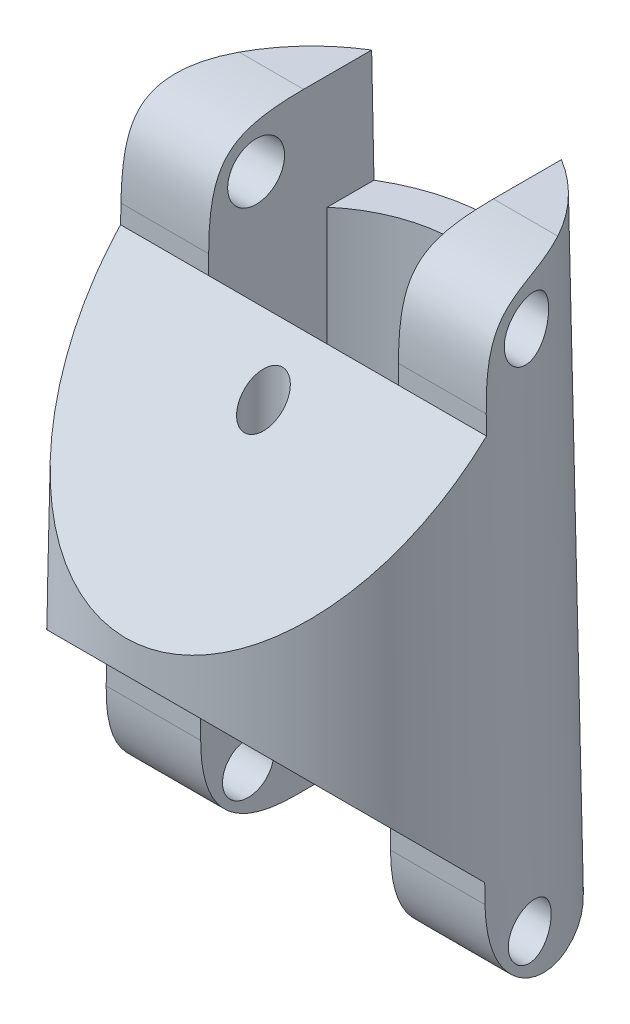
SolidWorks part; units mm, degrees
material "ABS"
ref_plane "Front Plane" through (0, 0, 0) normal (0, 0, 1) x (1, 0, 0)
ref_plane "Top Plane" through (0, 0, 0) normal (0, 1, 0) x (1, 0, 0)
ref_plane "Right Plane" through (0, 0, 0) normal (1, 0, 0) x (0, 0, -1)
sketch "Sketch1" plane through (0, 0, 0) normal (0, 1, 0) x (1, 0, 0)
  circle A0 centre (0, 0) radius 10
  dimension "D1" = 20
extrude "Boss-Extrude1" add sketch "Sketch1" along normal blind 26 draft 1 and the other way blind 6 draft 1
sketch "Sketch2" plane through (0, 0, 0) normal (1, 0, 0) x (0, 0, -1)
  line L0 (-0.4538, 26) -> (-0.4538, 20)
  line L2 (9.5462, 26) -> (-9.5462, 26) construction
  line L3 (-0.4538, 20) -> (-13.1885, 7.2653)
  line L5 (-13.1885, 7.2653) -> (-13.1885, 26)
  line L6 (-13.1885, 26) -> (-0.4538, 26)
  dimension "D1" = 10
  dimension "D2" = 6
  dimension "D3" = 135
extrude "Cut-Extrude1" cut sketch "Sketch2" against normal through all both and the other way through all
sketch "Sketch3" plane through (0, 0, 0.4538) normal (0, 0, 1) x (1, 0, 0)
  line L0 (-9.6402, 20) -> (9.6402, 20) construction
  line L1 (5, 26) -> (-5, 26)
  line L2 (5, 26) -> (5, 20)
  line L3 (5, 20) -> (-5, 20)
  line L4 (-5, 26) -> (-5, 20)
  line L5 (5, 26) -> (-5, 20) construction
  line L6 (5, 20) -> (-5, 26) construction
  point P0 (0, 23)
  dimension "D1" = 10
  dimension "D2" = 6
extrude "Cut-Extrude2" cut sketch "Sketch3" against normal blind 25
sketch "Sketch4" plane through (-5, 0, 0) normal (1, 0, 0) x (0, 0, -1)
  circle A0 centre (2.0462, 23.5) radius 1.5
  dimension "D3" = 3
  dimension "D1" = 2.5
  dimension "D2" = 2.5
extrude "Cut-Extrude3" cut sketch "Sketch4" against normal through all both and the other way through all
fillet "Fillet2" radius 5 2 edges at (7.2677, 26, 0.4538) (-7.2677, 26, 0.4538)
sketch "Sketch7" plane through (0, 0, 0) normal (1, 0, 0) x (0, 0, -1)
  line L0 (-0.873, -6) -> (-0.873, 0)
  line L1 (-10.1047, -6) -> (10.1047, -6) construction
  line L2 (-0.873, 0) -> (-11.3178, 10.4448)
  line L3 (-11.3178, 10.4448) -> (-11.3178, -6)
  line L4 (-11.3178, -6) -> (-0.873, -6)
  dimension "D1" = 6
  dimension "D2" = 135
extrude "Cut-Extrude5" cut sketch "Sketch7" against normal through all both and the other way through all
sketch "Sketch8" plane through (0, 0, 0.873) normal (0, 0, 1) x (1, 0, 0)
  line L0 (-9.9618, 0) -> (9.9618, 0) construction
  line L1 (-5, -6) -> (5, -6)
  line L2 (-5, -6) -> (-5, 0)
  line L3 (-5, 0) -> (5, 0)
  line L4 (5, -6) -> (5, 0)
  line L5 (-5, -6) -> (5, 0) construction
  line L6 (-5, 0) -> (5, -6) construction
  point P0 (0, -3)
  dimension "D1" = 6
  dimension "D2" = 10
  dimension "D3" = 0
extrude "Cut-Extrude6" cut sketch "Sketch8" against normal through all
sketch "Sketch6" plane through (0, 20, 0) normal (0, 1, 0) x (1, 0, 0)
  line L0 (5, 8.2547) -> (5, -0.4538) construction
  line L1 (-5, -0.4538) -> (5, -0.4538) construction
  line L2 (-5, 8.2547) -> (-5, -0.4538) construction
  line L3 (5, 5.791) -> (5, -0.4538)
  line L4 (-5, -0.4538) -> (5, -0.4538)
  line L5 (-5, 5.791) -> (-5, -0.4538)
  arc A3 (3.9638, 6.544) -> (-3.9638, 6.544) centre (0, 0) ccw
  arc A4 (5, 5.791) -> (-5, 5.791) centre (0, 0) ccw
  dimension "D1" = 2
extrude "Cut-Extrude7" cut sketch "Sketch6" against normal through all contours A4 L5 L4 L3
sketch "Sketch9" plane through (-5, 0, 0) normal (1, 0, 0) x (0, 0, -1)
  circle A0 centre (1.627, -3.5) radius 1.3515
  dimension "D1" = 2.5
  dimension "D2" = 2.5
extrude "Cut-Extrude8" cut sketch "Sketch9" against normal through all both and the other way through all
fillet "Fillet3" radius 5 2 edges at (7.5335, -6, 0.873) (-7.5335, -6, 0.873)
sketch "Sketch10" plane through (0, 20, 0) normal (0, 1, 0) x (1, 0, 0)
  circle A0 centre (0, -2.5678) radius 1
  point P3 (0, 0)
extrude "Cut-Extrude9" cut sketch "Sketch10" against normal through all
